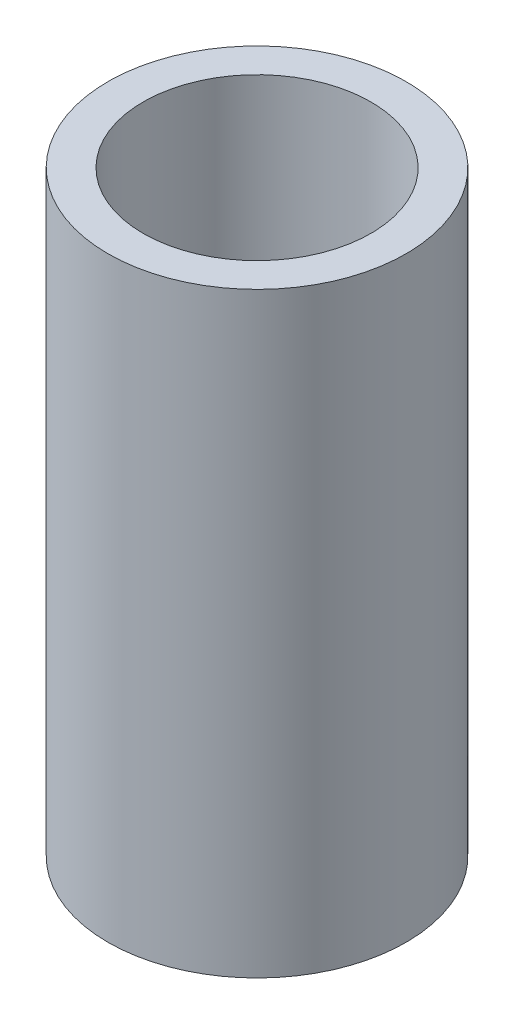
SolidWorks part; units mm, degrees
material "Plain Carbon Steel"
ref_plane "Front Plane" through (0, 0, 0) normal (0, 0, 1) x (1, 0, 0)
ref_plane "Top Plane" through (0, 0, 0) normal (0, 1, 0) x (1, 0, 0)
ref_plane "Right Plane" through (0, 0, 0) normal (1, 0, 0) x (0, 0, -1)
sketch "Sketch1" plane through (0, 0, 0) normal (0, 1, 0) x (1, 0, 0)
  circle A0 centre (0, 0) radius 43.6626
  circle A1 centre (0, 0) radius 57.15
  dimension "D1" = 87.3252
  dimension "D2" = 114.3
extrude "Extrude1" add sketch "Sketch1" along normal blind 228.6
equation "\"D1@Sketch1\" = \"D2@Sketch1\" - .531*2"
